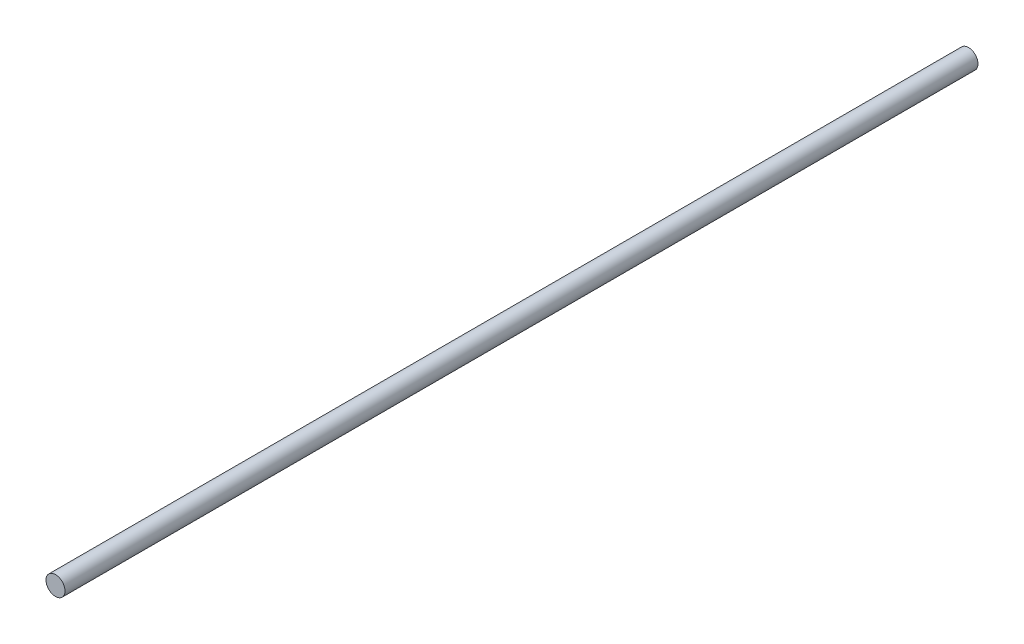
SolidWorks part; units mm, degrees
ref_plane "Front Plane" through (0, 0, 0) normal (0, 0, 1) x (1, 0, 0)
ref_plane "Top Plane" through (0, 0, 0) normal (0, 1, 0) x (1, 0, 0)
ref_plane "Right Plane" through (0, 0, 0) normal (1, 0, 0) x (0, 0, -1)
sketch "Sketch1" plane through (0, 0, 0) normal (0, 0, 1) x (1, 0, 0)
  line L1 (-3.175, 0) -> (3.175, 0) construction
  dimension "OD" = 6.35
sketch "Sketch2" plane through (0, 0, 0) normal (1, 0, 0) x (0, 0, -1)
  line L0 (152.4, 0) -> (-152.4, 0)
  point P4 (0, 0)
  dimension "Length" = 304.8
sketch "Sketch3" plane through (0, 0, 0) normal (0, 0, 1) x (1, 0, 0)
  circle A0 centre (0, 0) radius 3.175
extrude "Boss-Extrude1" add sketch "Sketch3" along normal up to vertex (152.4 mm away) and the other way up to vertex (152.4 mm away) up to point (0, 0, 152.4) other way up to point (0, 0, -152.4)
